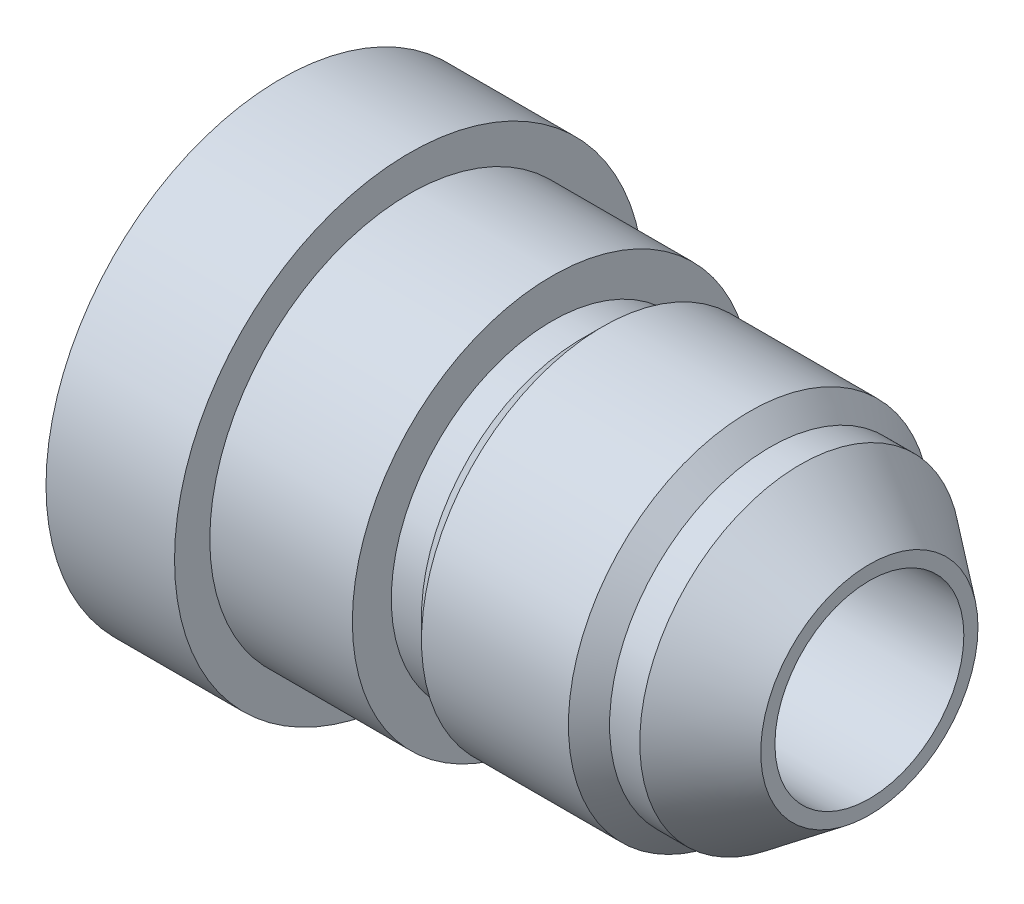
SolidWorks part; units mm, degrees
ref_plane "Front Plane" through (0, 0, 0) normal (0, 0, 1) x (1, 0, 0)
ref_plane "Top Plane" through (0, 0, 0) normal (0, 1, 0) x (1, 0, 0)
ref_plane "Right Plane" through (0, 0, 0) normal (1, 0, 0) x (0, 0, -1)
sketch "Sketch1" plane through (0, 0, 0) normal (0, 0, 1) x (1, 0, 0)
  line L0 (-15.4686, 0) -> (15.4686, 0) construction
  line L1 (-15.4686, 12.3444) -> (-15.4686, 11.176)
  line L2 (-15.4686, 11.176) -> (-7.2273, 4.9657)
  line L3 (-7.2273, 4.9657) -> (15.4686, 4.9657)
  line L4 (15.4686, 4.9657) -> (15.4686, 5.7106)
  line L5 (15.4686, 5.7106) -> (10.4067, 9.525) construction
  line L6 (10.4067, 9.525) -> (-1.2192, 9.525)
  line L7 (-1.2192, 10.4902) -> (-1.2192, 9.525)
  line L8 (-1.2192, 10.4902) -> (-8.7122, 10.4902)
  line L9 (-15.4686, 12.3444) -> (-8.7122, 12.3444)
  line L10 (-8.7122, 12.3444) -> (-8.7122, 10.4902)
  line L11 (10.4067, 9.525) -> (15.4686, 9.525)
  line L12 (15.4686, 9.525) -> (15.4686, 5.7106)
  dimension "A" = 30.9372
  dimension "OD" = 19.05
  dimension "Min" = 9.9314
  dimension "D3" = 11.4211
  dimension "D4" = 37
  dimension "B" = 6.7564
  dimension "G" = 24.6888
  dimension "C" = 16.6878
  dimension "F" = 20.9804
  dimension "D" = 22.352
revolve "Revolve1" add sketch "Sketch1" angle 360 about L0
ref_plane "Plane1" through (15.4686, 0, 0) normal (1, 0, 0) x (0, 0, -1)
sketch "Sketch2" plane through (15.4686, 0, 0) normal (1, 0, 0) x (0, 0, -1)
  circle A0 centre (0, 0) radius 9.525
curve "Helix/Spiral1" pitch 1.5875 height 16.6878 radius 9.525 centre (15.4686, 0, 0) axis (-1, 0, 0) start towards (0, 1, 0) parameters "Pitch"=1.5875
sketch "Sketch4" plane through (0, 0, 0) normal (0, 0, 1) x (1, 0, 0)
  line L0 (15.4686, 9.525) -> (16.8577, 9.525)
  line L1 (15.4686, 9.525) -> (16.0639, 8.4939)
  line L2 (16.0639, 8.4939) -> (16.2623, 8.4939)
  line L3 (16.2623, 8.4939) -> (16.8577, 9.525)
  line L4 (16.1631, 8.4939) -> (16.1631, 9.525) construction
  line L5 (15.7663, 9.0094) -> (16.56, 9.0094) construction
  line L6 (15.4686, -9.525) -> (15.4686, 9.525) construction
  dimension "D1" = 60
  dimension "D2" = 0.1984
  dimension "D3" = 0.7937
sweep "Cut-Sweep1" cut profiles "Sketch4" path "Helix/Spiral1" align with end faces yes
sketch "Sketch5" plane through (0, 0, 0) normal (0, 0, 1) x (1, 0, 0)
  line L0 (15.4686, 5.7106) -> (11.8424, 8.4431)
  line L1 (11.8424, 8.4431) -> (10.2549, 8.4431)
  line L2 (10.2549, 8.4431) -> (9.173, 9.525)
  line L3 (9.173, 9.525) -> (15.4686, 9.525)
  line L4 (15.4686, 9.525) -> (15.4686, 5.7106)
  line L5 (15.4686, 5.7106) -> (10.4067, 9.525) construction
  line L6 (10.4067, 9.525) -> (-1.2192, 9.525) construction
  line L7 (-1.2192, 9.525) -> (-1.2192, 8.4431)
  line L8 (-1.2192, 8.4431) -> (0.3683, 8.4431)
  line L9 (0.3683, 8.4431) -> (1.4502, 9.525)
  line L10 (-1.2192, 9.525) -> (1.4502, 9.525)
  line L11 (0, 0) -> (-15.4686, 0) construction
  line L12 (8.2705, 9.525) -> (8.2705, -9.525) construction
  line L13 (0, 0) -> (8.2705, 0) construction
  point P21 (8.2705, -9.525)
  dimension "D1" = 45
  dimension "D2" = 0.0508
  dimension "D3" = 1.5875
  dimension "D4" = 45
  dimension "D5" = 1.9844
revolve "Cut-Revolve1" cut sketch "Sketch5" angle 360 about L11
sketch "Sketch6" plane through (0, 0, 0) normal (0, 0, 1) x (1, 0, 0)
  line L0 (1.4502, 9.525) -> (0.3683, 8.4431)
  line L1 (0.3683, 8.4431) -> (10.2549, 8.4431)
  line L2 (10.2549, 8.4431) -> (9.173, 9.525)
  line L3 (9.173, 9.525) -> (1.4502, 9.525)
  line L4 (-15.4686, 0) -> (8.2705, 0) construction
revolve "Revolve2" add sketch "Sketch6" angle 360 about L4
other "CPoint1" parameters "Diameter"=12.7, "StubLength"=0
ref_axis "Axis1" through (25.4686, 0, 0) along (-1, 0, 0)
equation "\"D3@Sketch1\" = \"Min@Sketch1\"*1.15"
equation "\"D3@Helix/Spiral1\" = \"C@Sketch1\""
equation "\"D2@Sketch4\" = \"Pitch@Helix/Spiral1\"*.125"
equation "\"D3@Sketch4\" = \"Pitch@Helix/Spiral1\"*.50"
equation "\"D3@Sketch5\" = \"Pitch@Helix/Spiral1\"*1."
equation "\"D5@Sketch5\" = \"Pitch@Helix/Spiral1\"*1.25"
